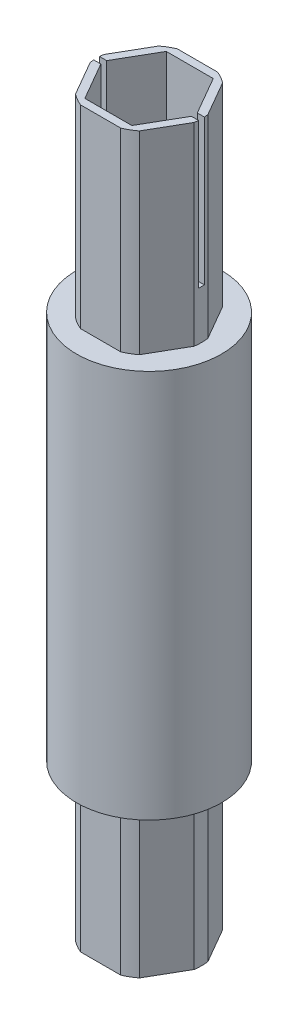
SolidWorks part; units mm, degrees
material "PET"
ref_plane "Front Plane" through (0, 0, 0) normal (0, 0, 1) x (1, 0, 0)
ref_plane "Top Plane" through (0, 0, 0) normal (0, 1, 0) x (1, 0, 0)
ref_plane "Right Plane" through (0, 0, 0) normal (1, 0, 0) x (0, 0, -1)
sketch "Sketch1" plane through (0, 0, 0) normal (0, 1, 0) x (1, 0, 0)
  line L1 (6.8168, 0.893) -> (4.1818, 5.457)
  line L2 (2.635, 6.35) -> (-2.635, 6.35)
  line L3 (-4.1818, 5.457) -> (-6.8168, 0.893)
  line L4 (-6.8168, -0.893) -> (-4.1818, -5.457)
  line L5 (-2.635, -6.35) -> (2.635, -6.35)
  line L6 (4.1818, -5.457) -> (6.8168, -0.893)
  circle A0 centre (0, 0) radius 6.35 construction
  arc A1 (-2.635, 6.35) -> (-4.1818, 5.457) centre (0, 0) ccw
  arc A2 (4.1818, 5.457) -> (2.635, 6.35) centre (0, 0) ccw
  arc A3 (6.8168, -0.893) -> (6.8168, 0.893) centre (0, 0) ccw
  arc A4 (2.635, -6.35) -> (4.1818, -5.457) centre (0, 0) ccw
  arc A5 (-4.1818, -5.457) -> (-2.635, -6.35) centre (0, 0) ccw
  arc A6 (-6.8168, 0.893) -> (-6.8168, -0.893) centre (0, 0) ccw
  dimension "D1" = 12.7
  dimension "D2" = 13.75
extrude "Boss-Extrude1" add sketch "Sketch1" against normal blind 19.812
sketch "Sketch2" plane through (0, 0, 0) normal (0, -1, 0) x (-1, 0, 0)
  circle A0 centre (0, 0) radius 9.5
  dimension "D1" = 19
extrude "Boss-Extrude2" add sketch "Sketch2" against normal blind 50.927
extrude "Boss-Extrude6" add sketch "Sketch1<4>" along normal blind 76.327
sketch "Sketch1<4>" plane through (0, 0, 0) normal (0, 1, 0) x (1, 0, 0) same geometry as "Sketch1"
sketch "Sketch6" plane through (0, 76.327, 0) normal (0, 1, 0) x (1, 0, 0)
  line L1 (-6.875, 0.381) -> (6.875, 0.381)
  line L2 (-6.875, 0.381) -> (-6.875, -0.381)
  line L3 (-6.875, -0.381) -> (6.875, -0.381)
  line L4 (6.875, 0.381) -> (6.875, -0.381)
  line L5 (-6.875, 0.381) -> (6.875, -0.381) construction
  line L6 (-6.875, -0.381) -> (6.875, 0.381) construction
  arc A0 (6.8168, -0.893) -> (6.8168, 0.893) centre (0, 0) ccw construction
  point P0 (0, 0)
  dimension "D1" = 0.762
extrude "Cut-Extrude1" cut sketch "Sketch6" against normal blind 19.05
sketch "Sketch7" plane through (0, 76.327, 0) normal (0, 1, 0) x (1, 0, 0)
  line L1 (4.0415, 0) -> (2.0207, 3.5) construction
  line L2 (2.0207, 3.5) -> (-2.0207, 3.5) construction
  line L3 (-2.0207, 3.5) -> (-4.0415, 0) construction
  line L4 (-4.0415, 0) -> (-2.0207, -3.5) construction
  line L5 (-2.0207, -3.5) -> (2.0207, -3.5) construction
  line L6 (2.0207, -3.5) -> (4.0415, 0) construction
  line L8 (3.0796, 5.334) -> (-3.0796, 5.334)
  line L9 (-3.0796, 5.334) -> (-6.1592, 0)
  line L10 (-6.1592, 0) -> (-3.0796, -5.334)
  line L11 (-3.0796, -5.334) -> (3.0796, -5.334)
  line L12 (3.0796, -5.334) -> (6.1592, 0)
  line L13 (6.1592, 0) -> (3.0796, 5.334)
  circle A0 centre (0, 0) radius 3.5 construction
  circle A1 centre (0, 0) radius 5.334 construction
  dimension "D1" = 7
  dimension "D2" = 10.668
extrude "Cut-Extrude2" cut sketch "Sketch7" against normal blind 29.017
